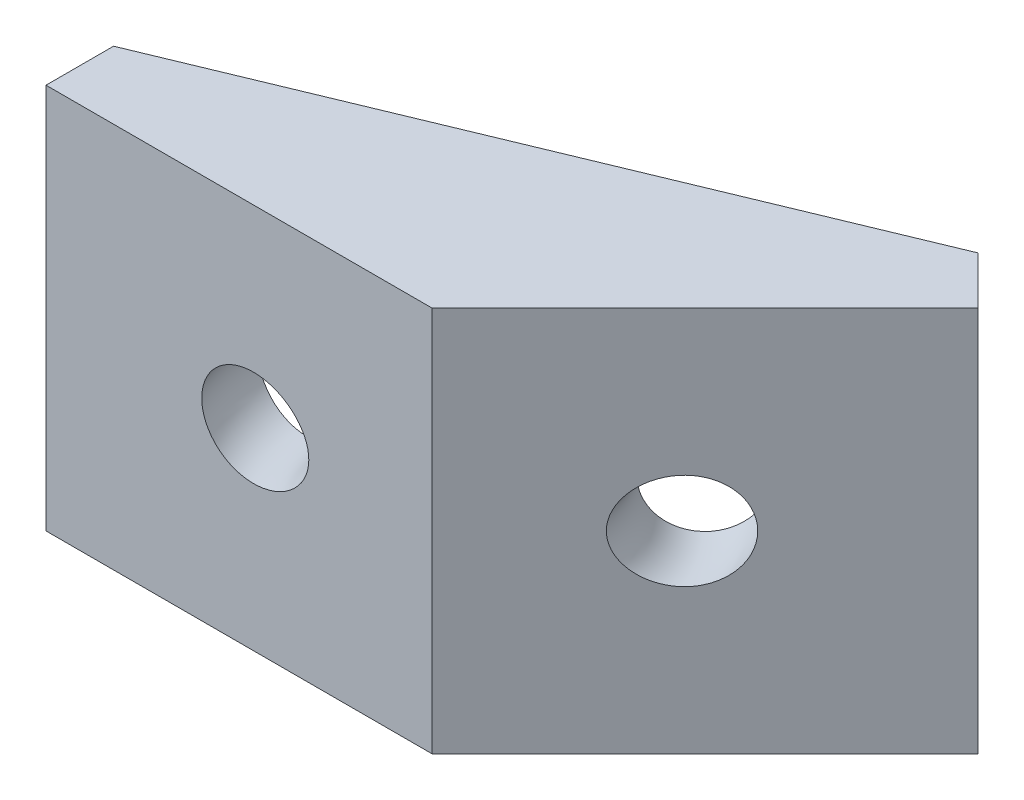
SolidWorks part; units mm, degrees
ref_plane "Front Plane" through (0, 0, 0) normal (0, 0, 1) x (1, 0, 0)
ref_plane "Top Plane" through (0, 0, 0) normal (0, 1, 0) x (1, 0, 0)
ref_plane "Right Plane" through (0, 0, 0) normal (1, 0, 0) x (0, 0, -1)
sketch "Sketch1" plane through (0, 0, 0) normal (0, 1, 0) x (1, 0, 0)
  line L0 (-20, 3.5) -> (-1.4497, 3.5)
  line L3 (-20, 0) -> (0, 0)
  line L4 (14.1421, 14.1421) -> (0, 0)
  line L5 (-1.4497, 3.5) -> (11.6673, 16.617)
  line L6 (-20, 0) -> (-20, 3.5)
  line L7 (11.6673, 16.617) -> (14.1421, 14.1421)
  dimension "D1" = 135
  dimension "D2" = 3.5
  dimension "D3" = 3.5
  dimension "D4" = 20
  dimension "D5" = 20
extrude "Boss-Extrude1" add sketch "Sketch1" along normal blind 20
sketch "Sketch2" plane through (0, 20, 0) normal (0, 1, 0) x (1, 0, 0)
  line L0 (-20, 3.5) -> (11.6673, 16.617)
  line L1 (11.6673, 16.617) -> (-1.4497, 3.5)
  line L2 (-1.4497, 3.5) -> (-20, 3.5)
extrude "Boss-Extrude2" add sketch "Sketch2" against normal blind 2
extrude "Boss-Extrude3" add sketch "Sketch2<2>" along normal blind 2 from surface starting at face at (-2.6067, 0, -6.2932)
sketch "Sketch2<2>" plane through (0, 20, 0) normal (0, 1, 0) x (1, 0, 0) same geometry as "Sketch2"
sketch "Sketch3" plane through (0, 0, -3.5) normal (0, 0, -1) x (-1, 0, 0)
  line L0 (1.4453, 10) -> (20, 10) construction
  line L1 (20, 18) -> (20, 2) construction
  circle A0 centre (10, 10) radius 2.5
  dimension "D1" = 5
  dimension "D2" = 10
revolve "Cut-Revolve1" cut sketch "Sketch3" angle 360 about axis through (-1.4497, 20, -3.5) along (0, -1, 0)
